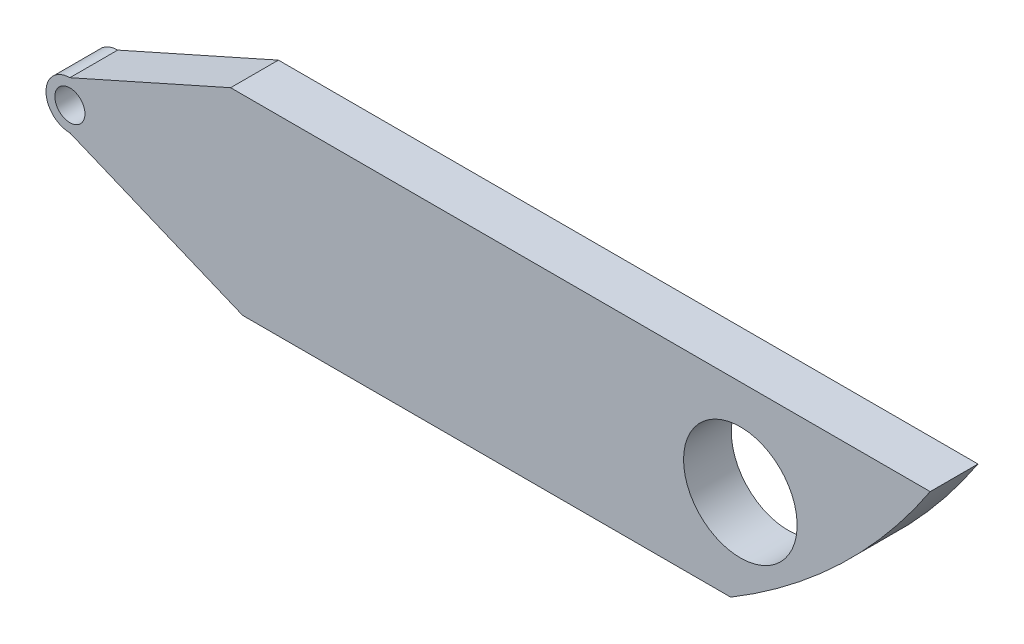
SolidWorks part; units mm, degrees
ref_plane "Front Plane" through (0, 0, 0) normal (0, 0, 1) x (1, 0, 0)
ref_plane "Top Plane" through (0, 0, 0) normal (0, 1, 0) x (1, 0, 0)
ref_plane "Right Plane" through (0, 0, 0) normal (1, 0, 0) x (0, 0, -1)
sketch "Sketch1" plane through (0, 0, 0) normal (0, 0, 1) x (1, 0, 0)
  line L1 (120.65, 25.4) -> (-120.65, 25.4)
  line L2 (120.65, 25.4) -> (120.65, -25.4)
  line L3 (120.65, -25.4) -> (-120.65, -25.4)
  line L4 (-120.65, 25.4) -> (-120.65, -25.4)
  line L5 (120.65, 25.4) -> (-120.65, -25.4) construction
  line L6 (120.65, -25.4) -> (-120.65, 25.4) construction
  point P0 (0, 0)
  dimension "D1" = 241.3
  dimension "D2" = 50.8
extrude "Boss-Extrude1" add sketch "Sketch1" along normal blind 12.7
sketch "Sketch3" plane through (0, 0, 12.7) normal (0, 0, 1) x (1, 0, 0)
  line L0 (0, 0) -> (-120.65, 0) construction
  line L1 (-120.65, 25.4) -> (-120.65, -25.4) construction
  circle A0 centre (-107.95, 0) radius 4
  dimension "D2" = 8
  dimension "D1" = 12.7
extrude "Cut-Extrude1" cut sketch "Sketch3" against normal through all
sketch "Sketch5" plane through (0, 0, 12.7) normal (0, 0, 1) x (1, 0, 0)
  line L0 (-120.65, -25.4) -> (120.65, -25.4) construction
  line L1 (-107.95, -6.35) -> (-62.0461, -25.4)
  line L2 (-107.95, 6.35) -> (-65.2393, 25.4)
  line L3 (120.65, 25.4) -> (-120.65, 25.4) construction
  line L4 (-65.2393, 25.4) -> (-120.65, 25.4)
  line L5 (-120.65, 25.4) -> (-120.65, -25.4)
  line L6 (-120.65, -25.4) -> (-62.0461, -25.4)
  line L7 (120.65, 25.4) -> (120.65, -25.4)
  line L8 (120.65, -25.4) -> (67.6371, -25.4)
  arc A0 (67.6371, -25.4) -> (120.65, 25.4) centre (-17.2255, 116.2204) ccw
  arc A2 (-107.95, 6.35) -> (-107.95, -6.35) centre (-107.95, 0) ccw
  point P15 (53.5409, -25.4)
  point P20 (0, 0)
  point P22 (67.6371, -25.4)
  line M3 (-120.65, 25.4) -> (-120.65, -25.4)
  line M4 (-120.65, -25.4) -> (120.65, -25.4)
  line M5 (120.65, -25.4) -> (120.65, 25.4)
  line M6 (120.65, 25.4) -> (-120.65, 25.4)
  dimension "D1" = 165.1
  dimension "D2" = 12.7
extrude "Cut-Extrude2" cut sketch "Sketch5" against normal through all contours A0 L8 M5 | A2 L2 L1 M6 M3 M4 region at (-85.2953, -16.5913, 12.7) region at (104.3429, -9.7563, 12.7)
sketch "Sketch6" plane through (0, 0, 12.7) normal (0, 0, 1) x (1, 0, 0)
  line L0 (-107.95, 0) -> (100.0384, 0) construction
  arc A0 (67.6371, -25.4) -> (120.65, 25.4) centre (-17.2255, 116.2204) ccw construction
  circle A1 centre (19.05, 0) radius 3.1347
  dimension "D1" = 127
sketch "Sketch7" plane through (0, 0, 0) normal (0, 0, -1) x (-1, 0, 0)
  line L0 (44.0204, -2.9977) -> (44.0204, 16.0523) construction
  point P3 (44.0204, -2.9977)
  point P4 (44.0204, 16.0523)
  dimension "D1" = 19.05
sketch "Sketch11" plane through (0, 0, 0) normal (0, 0, -1) x (-1, 0, 0)
  line L1 (107.95, 0) -> (-100.0384, 0) construction
  circle A1 centre (-70.2, 0) radius 15.09
  circle A2 centre (107.95, 0) radius 4 construction
  point P4 (-89.29, 0)
  dimension "D1" = 30.18
  dimension "D2" = 178.15
extrude "Cut-Extrude3" cut sketch "Sketch11" against normal through all
